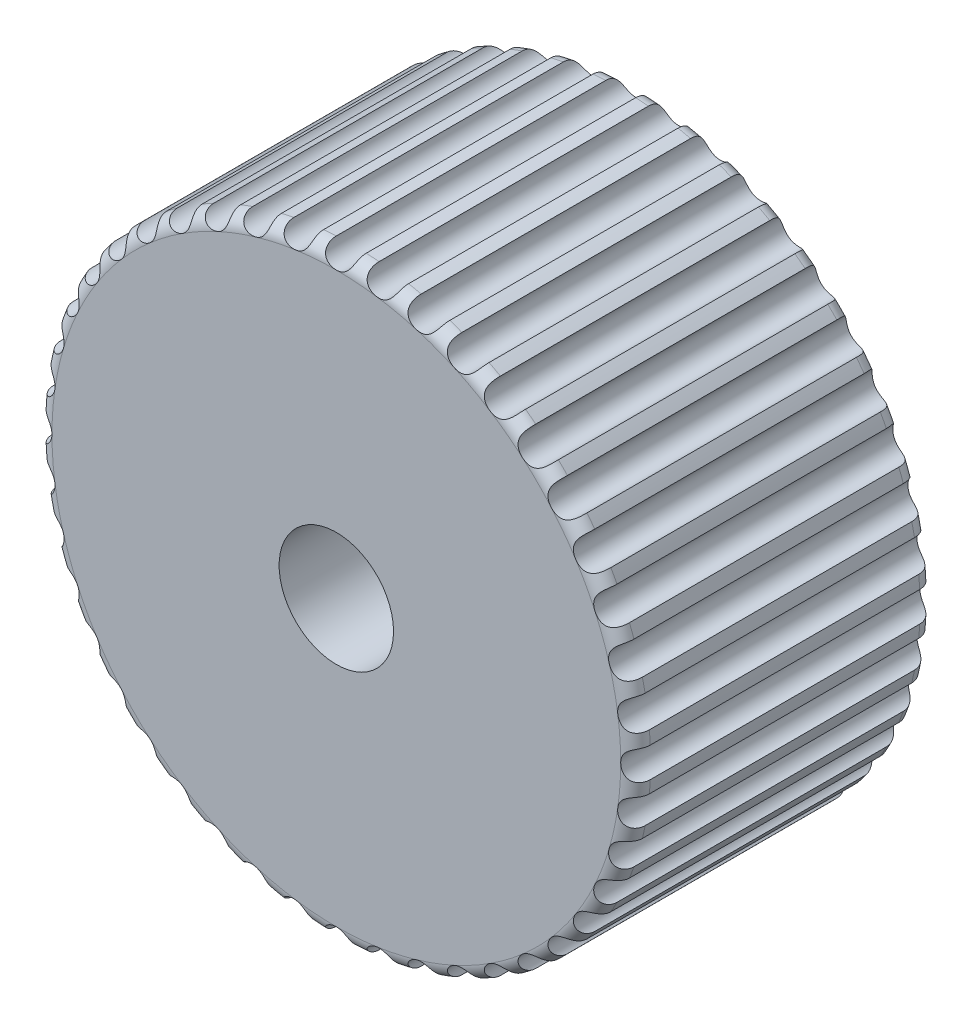
SolidWorks part; units mm, degrees
ref_plane "Front Plane" through (0, 0, 0) normal (0, 0, 1) x (1, 0, 0)
ref_plane "Top Plane" through (0, 0, 0) normal (0, 1, 0) x (1, 0, 0)
ref_plane "Right Plane" through (0, 0, 0) normal (1, 0, 0) x (0, 0, -1)
sketch "Sketch1" plane through (0, 0, 0) normal (0, 0, 1) x (1, 0, 0)
  circle A0 centre (1.3502, -4.6006) radius 0.3822
  circle A1 centre (1.3502, -4.6006) radius 2
  spline S4 degree 5 poles (1.3502, -4.9828) (1.4703, -4.9828) (1.5905, -4.9358) (1.6854, -4.8407) (1.7794, -4.6006) (1.6854, -4.3604) (1.5905, -4.2653) (1.4703, -4.2183) (1.3502, -4.2183) knots 4.92139 4.92139 4.92139 4.92139 4.92139 4.92139 7.382085 7.382085 7.382085 9.842779 9.842779 9.842779 9.842779 9.842779 9.842779 construction
  spline S5 degree 5 poles (1.3502, -4.2183) (1.2301, -4.2183) (1.1099, -4.2653) (1.015, -4.3604) (0.9209, -4.6006) (1.015, -4.8407) (1.1099, -4.9358) (1.2301, -4.9828) (1.3502, -4.9828) knots 0 0 0 0 0 0 2.460695 2.460695 2.460695 4.92139 4.92139 4.92139 4.92139 4.92139 4.92139 construction
  point P2 (1.7324, -4.6006)
  dimension "D2" = 4
extrude "Boss-Extrude1" add sketch "Sketch1" along normal blind 2
extrude "Boss-Extrude2" add sketch "Sketch1<2>" along normal blind 1 contours A0 region at (1.3502, -4.6006, 0)
sketch "Sketch1<2>" plane through (0, 0, 0) normal (0, 0, 1) x (1, 0, 0) same geometry as "Sketch1"
fillet "Fillet1" radius 0.1 2 edges at (3.3502, -4.6006, 2) (3.3502, -4.6006, 0)
sketch "Sketch2" plane through (0, 0, 0) normal (0, 0, -1) x (-1, 0, 0)
  circle A0 centre (-1.3502, -2.6006) radius 0.1
  circle A1 centre (-1.3502, -4.6006) radius 2 construction
  dimension "D1" = 0.2
extrude "Cut-Extrude1" cut sketch "Sketch2" against normal through all
pattern_circular "CirPattern1" count 44 over 360 about axis through (1.3502, -4.6006, 2) along (0, 0, -1) of "Cut-Extrude1"
